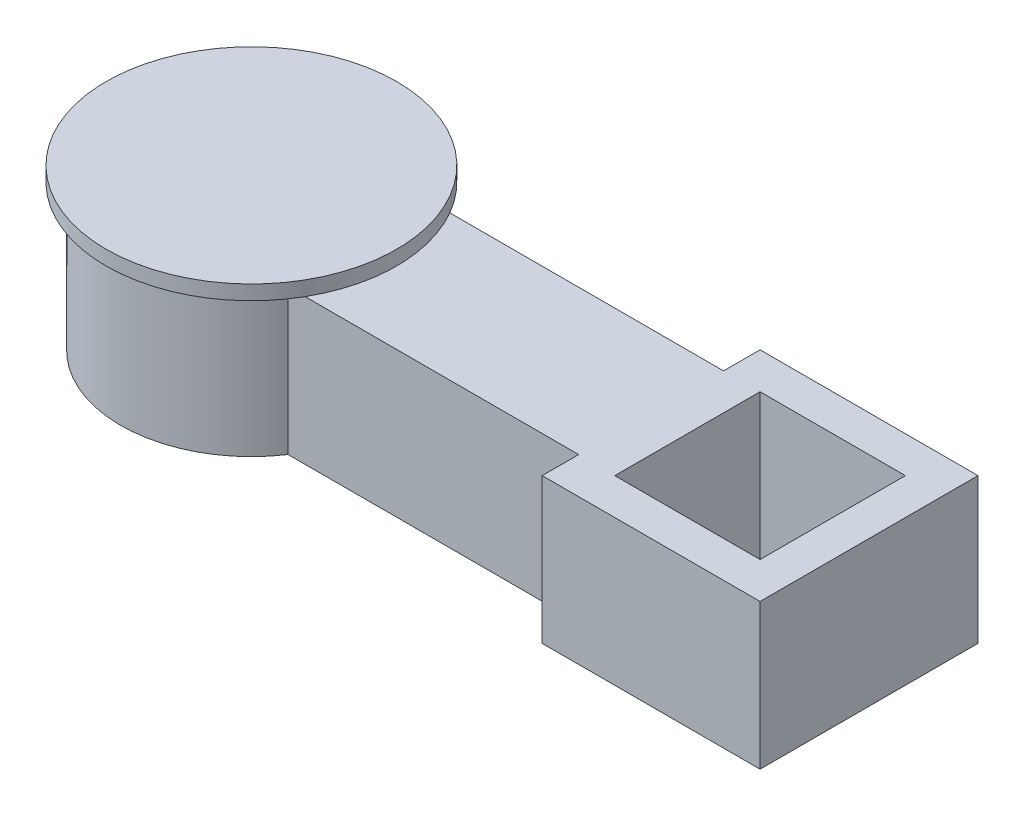
SolidWorks part; units mm, degrees
ref_plane "Front Plane" through (0, 0, 0) normal (0, 0, 1) x (1, 0, 0)
ref_plane "Top Plane" through (0, 0, 0) normal (0, 1, 0) x (1, 0, 0)
ref_plane "Right Plane" through (0, 0, 0) normal (1, 0, 0) x (0, 0, -1)
sketch "Sketch1" plane through (0, 0, 0) normal (0, 1, 0) x (1, 0, 0)
  line L0 (363.1456, 275.7418) -> (363.1456, 275.9924)
  line L1 (363.1456, 175.9924) -> (563.1456, 175.9924)
  line L2 (363.1456, 175.9924) -> (363.1456, 176.2431)
  line L3 (363.1456, 275.9924) -> (563.1456, 275.9924)
  line L4 (563.1456, 175.9924) -> (563.1456, 176.2431)
  line L5 (563.1456, 275.7418) -> (563.1456, 275.9924)
  line L8 (363.1456, 275.9924) -> (563.1456, 275.9924)
  line L9 (363.1456, 275.9924) -> (363.1456, 275.7418)
  line L10 (363.1456, 176.2431) -> (563.1456, 176.2431)
  line L11 (563.1456, 275.9924) -> (563.1456, 176.2431)
  line L12 (563.1456, 301.1178) -> (713.1456, 301.1178)
  line L13 (563.1456, 301.1178) -> (563.1456, 151.1178)
  line L14 (563.1456, 151.1178) -> (713.1456, 151.1178)
  line L15 (713.1456, 301.1178) -> (713.1456, 151.1178)
  arc A0 (363.1456, 275.7418) -> (363.1456, 176.2431) centre (288.1456, 225.9924) ccw
  point P13 (713.1456, 226.1178)
  point P14 (563.1456, 226.1178)
  dimension "D3" = 180
  dimension "D6" = 150
  dimension "D1" = 200
  dimension "D2" = 100
  dimension "D4" = 50
  dimension "D5" = 75
  dimension "D7" = 150
extrude "Boss-Extrude1" add sketch "Sketch1" along normal blind 100 contours L0 A0 L10 L11 L5 L3 | L13 L12 L15 L14 region at (364.9558, 0, -226.0488)
sketch "Sketch5" plane through (0, 100, 0) normal (0, 1, 0) x (1, 0, 0)
  circle A0 centre (288.1456, 225.9924) radius 70
  dimension "D1" = 140
extrude "Cut-Extrude2" cut sketch "Sketch5" against normal blind 100
sketch "Sketch6" plane through (0, 100, 0) normal (0, 1, 0) x (1, 0, 0)
  circle A0 centre (288.1456, 225.9924) radius 100
  dimension "D1" = 200
extrude "Boss-Extrude4" add sketch "Sketch6" along normal blind 10
sketch "Sketch7" plane through (0, 100, 0) normal (0, 1, 0) x (1, 0, 0)
  line L0 (563.1456, 301.1178) -> (713.1456, 301.1178) construction
  line L1 (588.1456, 176.1178) -> (688.1456, 176.1178)
  line L2 (588.1456, 176.1178) -> (588.1456, 276.1178)
  line L3 (588.1456, 276.1178) -> (688.1456, 276.1178)
  line L4 (688.1456, 176.1178) -> (688.1456, 276.1178)
  line L5 (713.1456, 301.1178) -> (713.1456, 151.1178) construction
  point P6 (638.1456, 301.1178)
  point P7 (638.1456, 276.1178)
  point P10 (713.1456, 226.1178)
  point P11 (688.1456, 226.1178)
  dimension "D1" = 100
  dimension "D2" = 100
extrude "Cut-Extrude3" cut sketch "Sketch7" against normal blind 100
sketch "Sketch10" plane through (0, 0, 0) normal (0, -1, 0) x (-1, 0, 0)
  line L0 (-588.1456, 176.1178) -> (-688.1456, 276.1178)
  line L1 (-688.1456, 276.1178) -> (-688.1456, 176.1178)
  line L2 (-688.1456, 176.1178) -> (-588.1456, 276.1178)
  line L3 (-588.1456, 276.1178) -> (-688.1456, 276.1178)
